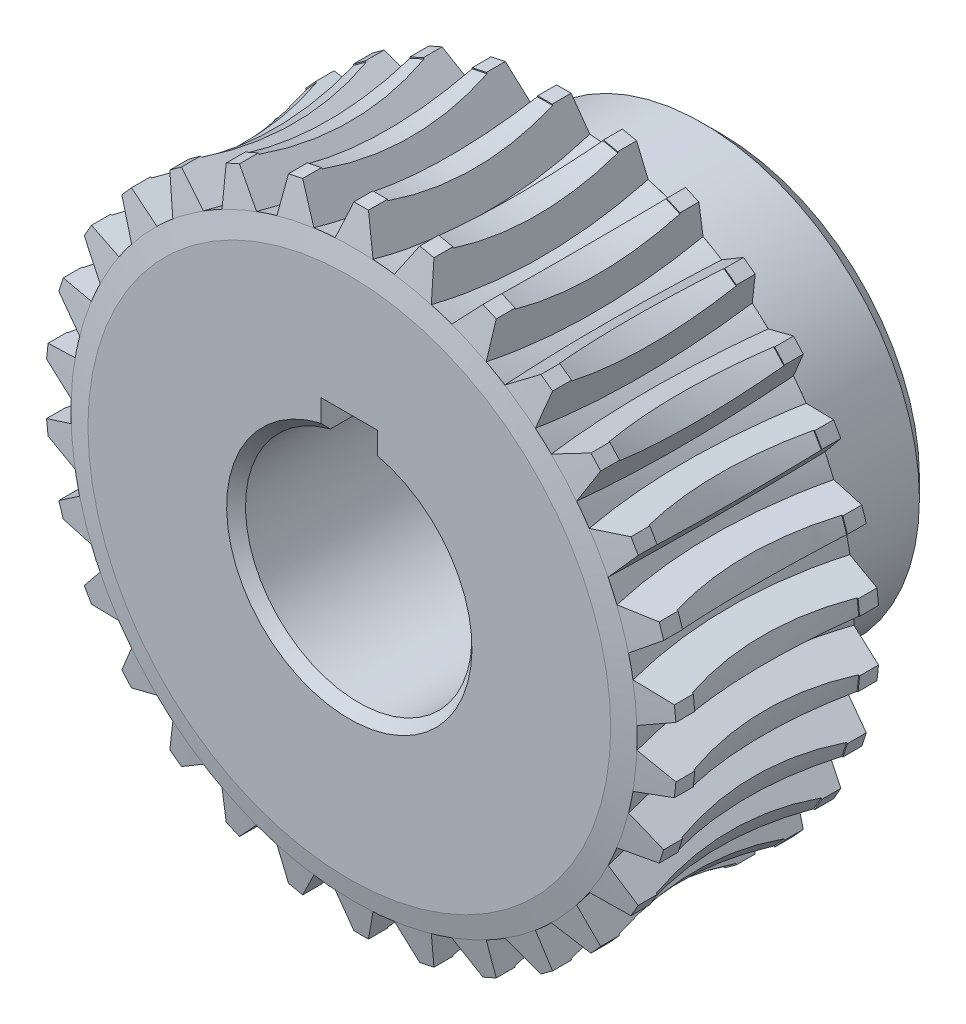
SolidWorks part; units mm, degrees
material "Phosphor bronze 10% D, UNS C52400"
ref_plane "Front Plane" through (0, 0, 0) normal (0, 0, 1) x (1, 0, 0)
ref_plane "Top Plane" through (0, 0, 0) normal (0, 1, 0) x (1, 0, 0)
ref_plane "Right Plane" through (0, 0, 0) normal (1, 0, 0) x (0, 0, -1)
sketch "Sketch1" plane through (0, 0, 0) normal (0, 0, 1) x (1, 0, 0)
  circle A0 centre (0, 0) radius 15
  dimension "D1" = 30
extrude "Boss-Extrude1" add sketch "Sketch1" along normal blind 12
sketch "Sketch2" plane through (0, 0, 0) normal (1, 0, 0) x (0, 0, -1)
  line L0 (0, 15) -> (0, 13.85)
  line L3 (-0.25, 15) -> (0, 15)
  line L4 (0, 13.85) -> (-0.25, 15)
  line L5 (-12, 15) -> (-12, -15) construction
  line L6 (-12, 13.85) -> (-11.75, 15)
  line L7 (-11.75, 15) -> (-12, 15)
  line L8 (-12, 15) -> (-12, 13.85)
  line L9 (-12, 0) -> (6.5144, 0)
revolve "Cut-Revolve1" cut sketch "Sketch2" angle 360 about L9 region at (0, 14.6167, 0.0833) region at (0, 14.6167, 11.9167)
sketch "Sketch3" plane through (0, 0, 0) normal (1, 0, 0) x (0, 0, -1)
  line L0 (-11.75, 15) -> (-0.25, 15)
  line L2 (-11.75, 15) -> (-11.75, -15) construction
  line L3 (-12, 0) -> (7.8424, 0)
  line L4 (-12, 13.85) -> (-12, -13.85) construction
  arc A1 (-0.25, 15) -> (-11.75, 15) centre (-6, 42.2199) cw
revolve "Cut-Revolve2" cut sketch "Sketch3" angle 360 about L3 region at (0, 14.7595, 6)
ref_plane "Plane1" through (0, 0, 0.25) normal (0, 0, -1) x (-1, 0, 0)
sketch "Sketch6" plane through (0, 0, 0.25) normal (0, 0, -1) x (-1, 0, 0)
  line L1 (-0.385, 16.725) -> (0.385, 16.725)
  line L4 (1, 14.9666) -> (1.3212, 14.0484)
  line L5 (-1, 14.9666) -> (-1.3212, 14.0484)
  line L6 (-0.385, 16.725) -> (-1, 14.9666)
  line L7 (0.385, 16.725) -> (1, 14.9666)
  line L8 (-1.3212, 14.0484) -> (1.3212, 14.0484)
  dimension "D2" = 0.77
extrude "Boss-Extrude2" add sketch "Sketch6" against normal blind 11.5
pattern_circular "CirPattern1" count 30 every 12 about axis through (0, 0, 0.25) along (0, 0, 1) of "Boss-Extrude2"
sketch "Sketch7" plane through (0, 0, 0) normal (1, 0, 0) x (0, 0, -1)
  line L0 (-11.75, 14.9703) -> (-11.2608, 17.2207)
  line L1 (-11.75, 15.1225) -> (-11.75, 13.266) construction
  line L2 (-11.2608, 17.2207) -> (-11.75, 17.2207)
  line L3 (-11.75, 17.2207) -> (-11.75, 14.9703)
  line L4 (0, 0) -> (-17.9273, 0)
  line L6 (-0.25, 17.2207) -> (-0.25, 14.9703)
  line L7 (-0.7392, 17.2207) -> (-0.25, 17.2207)
  line L8 (-0.25, 14.9703) -> (-0.7392, 17.2207)
revolve "Cut-Revolve3" cut sketch "Sketch7" angle 360 about L4 region at (0, 16.4706, 11.5869) region at (0, 16.4706, 0.4131)
sketch "Sketch8" plane through (0, 0, 0) normal (0, 1, 0) x (1, 0, 0)
  line L0 (0, 0) -> (0, -16.819)
  line L1 (-16.6736, -11.3676) -> (-16.6736, -0.6324) construction
  line L2 (13.85, 0) -> (-13.85, 0) construction
  line L3 (-16.6736, -1.6324) -> (-16.8635, -1.6324)
  line L4 (-16.8635, -1.6324) -> (-16.8635, -10.3676)
  line L5 (-16.8635, -10.3676) -> (-16.6736, -10.3676)
  arc A0 (-16.6736, -1.6324) -> (-16.6736, -10.3676) centre (-32.3277, -6) cw
revolve "Cut-Revolve4" cut sketch "Sketch8" angle 360 about L0 region at (-16.5418, 0, 6)
sketch "Sketch9" plane through (0, 0, 0) normal (0, 0, -1) x (-1, 0, 0)
  circle A0 centre (0, 0) radius 11.5
  dimension "D1" = 23
extrude "Boss-Extrude3" add sketch "Sketch9" along normal blind 7.71
sketch "Sketch10" plane through (0, 0, -7.71) normal (0, 0, -1) x (-1, 0, 0)
  circle A0 centre (0, 0) radius 6
  dimension "D1" = 12
extrude "Cut-Extrude2" cut sketch "Sketch10" against normal through all both and the other way through all
sketch "Sketch11" plane through (0, 0, -7.71) normal (0, 0, -1) x (-1, 0, 0)
  line L2 (-1.5, 0.8688) -> (1.5, 0.8688)
  line L3 (-1.5, 0.8688) -> (-1.5, 7.5)
  line L4 (-1.5, 7.5) -> (1.5, 7.5)
  line L5 (1.5, 0.8688) -> (1.5, 7.5)
  line L6 (-1.5, 0.8688) -> (1.5, 7.5) construction
  line L7 (-1.5, 7.5) -> (1.5, 0.8688) construction
  point P6 (0, 4.1844)
  dimension "D2" = 3
extrude "Cut-Extrude3" cut sketch "Sketch11" against normal through all both and the other way through all
chamfer "Chamfer1" distance 1 angle 45 1 edges at (-11.5, 0, -7.71)
chamfer "Chamfer2" distance 0.5 angle 45 2 edges at (0, -6, 12) (0, -6, -7.71)
